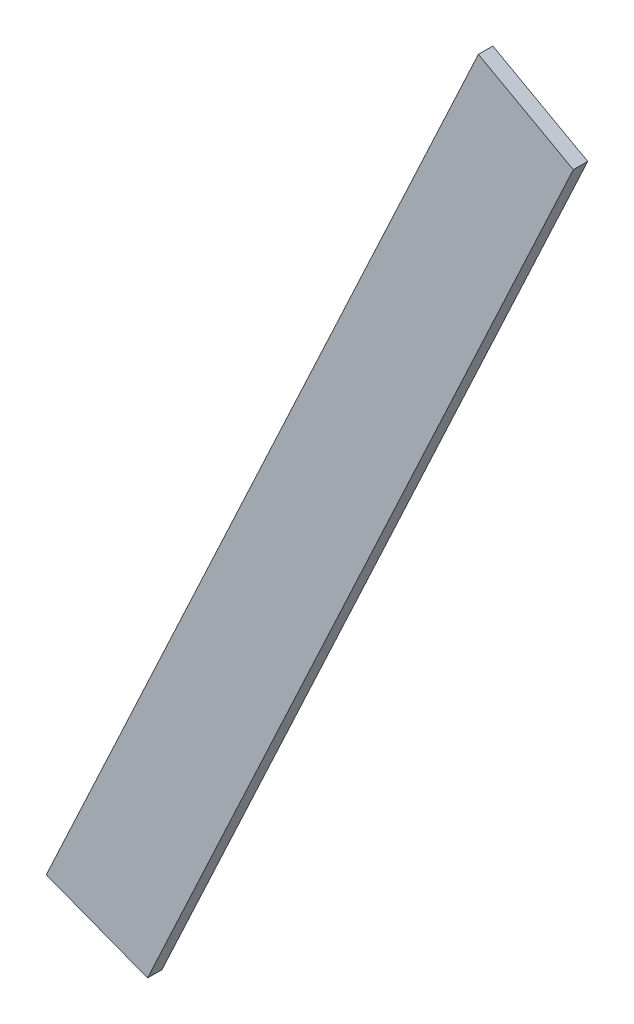
SolidWorks part; units mm, degrees
ref_plane "Front Plane" through (0, 0, 0) normal (0, 0, 1) x (1, 0, 0)
ref_plane "Top Plane" through (0, 0, 0) normal (0, 1, 0) x (1, 0, 0)
ref_plane "Right Plane" through (0, 0, 0) normal (1, 0, 0) x (0, 0, -1)
sketch "Sketch1" plane through (0, 0, 0) normal (0, 0, 1) x (1, 0, 0)
  line L0 (31.5265, -12.5038) -> (17.482, -7.1291)
  line L2 (17.482, -7.1291) -> (77.3951, 121.3387)
  line L4 (31.5265, -12.5038) -> (90.5529, 114.0628)
  line L5 (90.5529, 114.0628) -> (77.3951, 121.3387)
  line L6 (150.3865, 80.9766) -> (-24.6367, 177.7592) construction
  line L7 (-91.2666, 34.4877) -> (95.5228, -36.9945) construction
  dimension "D1" = 15
extrude "Boss-Extrude1" add sketch "Sketch1" along normal blind 2
ref_plane "Plane1" through (23.887, -11.1401, 0) normal (0.9063, -0.4227, 0) x (0, 0, -1)
